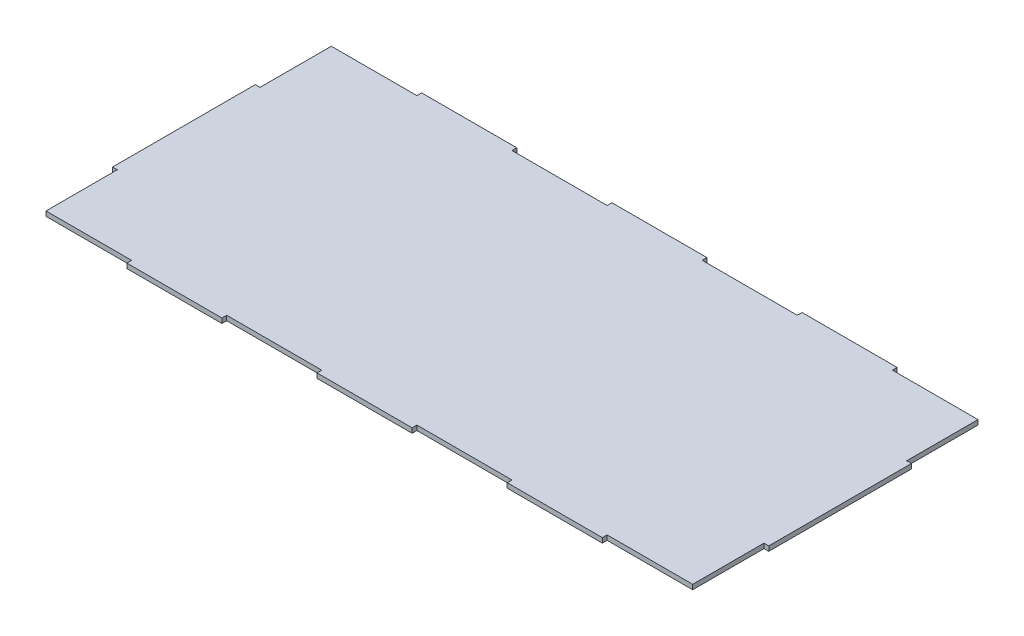
SolidWorks part; units mm, degrees
ref_plane "Ebene vorne" through (0, 0, 0) normal (0, 0, 1) x (1, 0, 0)
ref_plane "Ebene oben" through (0, 0, 0) normal (0, 1, 0) x (1, 0, 0)
ref_plane "Ebene rechts" through (0, 0, 0) normal (1, 0, 0) x (0, 0, -1)
sketch "Skizze1" plane through (0, 0, 0) normal (0, 1, 0) x (1, 0, 0)
  line L1 (-340, -150) -> (340, -150)
  line L2 (-340, -150) -> (-340, 150)
  line L3 (-340, 150) -> (340, 150)
  line L4 (340, -150) -> (340, 150)
  line L5 (-340, -150) -> (340, 150) construction
  line L6 (-340, 150) -> (340, -150) construction
  point P0 (0, 0)
  dimension "D1" = 680
  dimension "D2" = 300
extrude "Aufsatz-Linear austragen1" add sketch "Skizze1" along normal blind 5
sketch "Skizze2" plane through (0, 5, 0) normal (0, 1, 0) x (1, 0, 0)
  line L0 (-340, 0) -> (0, 0) construction
  line L1 (-340, 150) -> (-340, -150) construction
  line L2 (0, 0) -> (0, 150) construction
  line L3 (340, 150) -> (-340, 150) construction
  line L4 (50, 150) -> (-50, 150)
  line L5 (-50, 150) -> (-50, 155)
  line L6 (-50, 155) -> (50, 155)
  line L7 (50, 150) -> (50, 155)
  line L8 (-250, 150) -> (-150, 150)
  line L9 (-250, 150) -> (-250, 155)
  line L10 (-250, 155) -> (-150, 155)
  line L11 (-150, 150) -> (-150, 155)
  line L12 (150, 150) -> (150, 155)
  line L13 (250, 155) -> (150, 155)
  line L14 (250, 150) -> (250, 155)
  line L15 (250, 150) -> (150, 150)
  line L16 (250, -150) -> (150, -150)
  line L17 (250, -150) -> (250, -155)
  line L18 (250, -155) -> (150, -155)
  line L19 (150, -150) -> (150, -155)
  line L20 (-150, -150) -> (-150, -155)
  line L21 (-250, -155) -> (-150, -155)
  line L22 (-250, -150) -> (-250, -155)
  line L23 (-250, -150) -> (-150, -150)
  line L24 (50, -150) -> (50, -155)
  line L25 (-50, -155) -> (50, -155)
  line L26 (-50, -150) -> (-50, -155)
  line L27 (50, -150) -> (-50, -150)
  line L28 (-340, -75) -> (-340, 75)
  line L29 (-340, 75) -> (-345, 75)
  line L30 (-345, 75) -> (-345, -75)
  line L31 (-340, -75) -> (-345, -75)
  line L32 (340, -75) -> (345, -75)
  line L33 (345, 75) -> (345, -75)
  line L34 (340, 75) -> (345, 75)
  line L35 (340, -75) -> (340, 75)
  point P16 (0, 155)
  point P33 (0, -155)
  point P38 (-345, 0)
  point P43 (345, 0)
  dimension "D1" = 5
  dimension "D2" = 100
  dimension "D3" = 100
  dimension "D4" = 150
  dimension "D5" = 5
extrude "Aufsatz-Linear austragen3" add sketch "Skizze2" against normal up to surface (5 mm away) up to face at (0, 0, 0)
